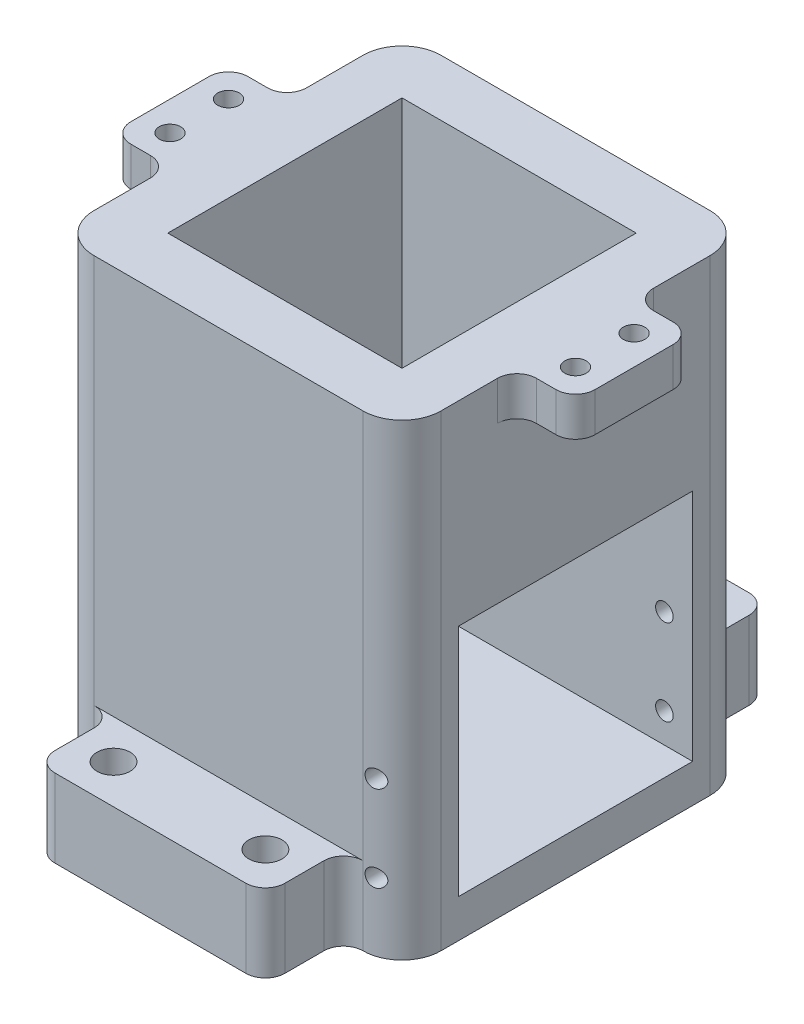
SolidWorks part; units mm, degrees
ref_plane "Front Plane" through (0, 0, 0) normal (0, 0, 1) x (1, 0, 0)
ref_plane "Top Plane" through (0, 0, 0) normal (0, 1, 0) x (1, 0, 0)
ref_plane "Right Plane" through (0, 0, 0) normal (1, 0, 0) x (0, 0, -1)
sketch "Sketch3" plane through (0, 0, 0) normal (0, 1, 0) x (1, 0, 0)
  line L1 (0, 0) -> (88.9, 0)
  line L2 (0, 0) -> (0, 88.9)
  line L3 (0, 88.9) -> (88.9, 88.9)
  line L4 (88.9, 0) -> (88.9, 88.9)
  dimension "D1" = 88.9
  dimension "D2" = 88.9
extrude "Boss-Extrude2" add sketch "Sketch3" along normal blind 50.8
ref_plane "Plane1" through (44.45, 0, 0) normal (-1, 0, 0) x (0, 0, 1)
sketch "Sketch5" plane through (0, 50.8, 0) normal (0, 1, 0) x (1, 0, 0)
  line L6 (0, 0) -> (88.9, 0)
  line L7 (0, 0) -> (0, 88.9)
  line L8 (0, 88.9) -> (88.9, 88.9)
  line L9 (88.9, 0) -> (88.9, 88.9)
sketch "Sketch7" plane through (0, 0, 0) normal (0, -1, 0) x (1, 0, 0)
  line L0 (44.45, -44.45) -> (65.45, -44.45)
  line L1 (44.45, 27.94) -> (44.45, -27.94) construction
  line L2 (65.45, -44.45) -> (65.45, -24.45)
  line L3 (65.45, -24.45) -> (23.45, -24.45)
  line L4 (23.45, -24.45) -> (23.45, -66.45)
  line L5 (23.45, -66.45) -> (65.45, -66.45)
  line L6 (65.45, -66.45) -> (65.45, -44.45)
  line L7 (44.45, -44.45) -> (44.45, -23.45)
  line L8 (44.45, -44.45) -> (44.45, -65.45)
  dimension "D1" = 21
  dimension "D3" = 42
  dimension "D4" = 42
  dimension "D5" = 21
  dimension "D6" = 21
sketch "Sketch10" plane through (0, 0, 0) normal (-1, 0, 0) x (0, 0, 1)
  line L1 (-73.9, 41) -> (-53.9, 41)
  line L2 (-73.9, 41) -> (-73.9, 61)
  line L3 (-73.9, 61) -> (-53.9, 61)
  line L4 (-53.9, 41) -> (-53.9, 61)
  line L5 (-88.9, 50.8) -> (-88.9, 0) construction
  line L6 (-35, 43.1973) -> (-15, 43.1973)
  line L7 (-35, 43.1973) -> (-35, 63.1973)
  line L8 (-35, 63.1973) -> (-15, 63.1973)
  line L9 (-15, 43.1973) -> (-15, 63.1973)
  line L11 (-88.9, 0) -> (0, 0) construction
  dimension "D1" = 20
  dimension "D2" = 20
  dimension "D3" = 20
  dimension "D4" = 20
  dimension "D5" = 18.9
  dimension "D6" = 15
  dimension "D7" = 41
sketch "Sketch11" plane through (88.9, 0, 0) normal (1, 0, 0) x (0, 0, -1)
  line L0 (0, 0) -> (88.9, 0) construction
  line L1 (15, 0) -> (35, 0)
  line L2 (15, 0) -> (15, 20)
  line L3 (15, 20) -> (35, 20)
  line L4 (35, 0) -> (35, 20)
  line L5 (0, 50.8) -> (0, 0) construction
  line L6 (53.9, 41) -> (73.9, 41)
  line L7 (53.9, 41) -> (53.9, 61)
  line L8 (53.9, 61) -> (73.9, 61)
  line L9 (73.9, 41) -> (73.9, 61)
  line L10 (88.9, 50.8) -> (88.9, 0) construction
  dimension "D1" = 20
  dimension "D2" = 20
  dimension "D3" = 15
  dimension "D4" = 15
sketch "Sketch13" plane through (0, 0, 0) normal (0, 0, 1) x (1, 0, 0)
  line L0 (44.45, 27.94) -> (44.45, -27.94) construction
  line L1 (0, 0) -> (88.9, 0) construction
  line L2 (88.9, 50.8) -> (88.9, 0) construction
  circle A0 centre (44.45, 20) radius 4.25
  dimension "D1" = 20
  dimension "D2" = 44.45
extrude "Cut-Extrude4" cut sketch "Sketch13" against normal blind 102
sketch "Sketch30" plane through (0, 50.8, 0) normal (0, 1, 0) x (1, 0, 0)
  line L1 (0, 0) -> (88.9, 0)
  line L2 (0, 0) -> (0, 88.9)
  line L3 (0, 88.9) -> (88.9, 88.9)
  line L4 (88.9, 0) -> (88.9, 88.9)
  line L5 (14.45, 74.45) -> (74.45, 74.45)
  line L6 (14.45, 74.45) -> (14.45, 14.45)
  line L7 (14.45, 14.45) -> (74.45, 14.45)
  line L8 (74.45, 74.45) -> (74.45, 14.45)
  dimension "D1" = 60
  dimension "D2" = 60
  dimension "D3" = 14.45
  dimension "D4" = 14.45
extrude "Boss-Extrude8" add sketch "Sketch30" along normal blind 110
sketch "Sketch31" plane through (0, 160.8, 0) normal (0, 1, 0) x (1, 0, 0)
  line L0 (0, 0) -> (0, 88.9) construction
  line L9 (0, 44.45) -> (-15, 44.45)
  line L10 (0, 44.45) -> (0, 59.45)
  line L11 (0, 59.45) -> (-15, 59.45)
  line L12 (-15, 44.45) -> (-15, 59.45)
  line L13 (88.9, 0) -> (88.9, 88.9) construction
  line L14 (0, 44.45) -> (-15, 44.45)
  line L15 (0, 44.45) -> (0, 29.45)
  line L16 (0, 29.45) -> (-15, 29.45)
  line L17 (-15, 44.45) -> (-15, 29.45)
  line L18 (88.9, 44.45) -> (103.9, 44.45)
  line L19 (88.9, 44.45) -> (88.9, 59.45)
  line L20 (88.9, 59.45) -> (103.9, 59.45)
  line L21 (103.9, 44.45) -> (103.9, 59.45)
  line L22 (0, 59.45) -> (0, 29.45)
  line L23 (88.9, 44.45) -> (103.9, 44.45)
  line L24 (88.9, 44.45) -> (88.9, 29.45)
  line L25 (88.9, 29.45) -> (103.9, 29.45)
  line L26 (103.9, 44.45) -> (103.9, 29.45)
  circle A6 centre (-7.5, 51.95) radius 2.75
  circle A7 centre (-7.5, 36.95) radius 2.75
  circle A8 centre (96.4, 51.95) radius 2.75
  circle A9 centre (96.4, 36.95) radius 2.75
  line M1 (0, 88.9) -> (0, 0)
  line M3 (88.9, 0) -> (88.9, 88.9)
  dimension "D1" = 15
  dimension "D5" = 15
  dimension "D2" = 15
  dimension "D3" = 15
  dimension "D4" = 15
  dimension "D6" = 15
  dimension "D7" = 15
  dimension "D8" = 15
extrude "Boss-Extrude10" add sketch "Sketch31" against normal blind 10 contours L12 L9 L11 A6 M1 | L9 L17 L16 A7 M1 | L18 L21 L20 A8 M3 | L26 L18 L25 A9 M3 region at (-0.2121, 160.8, -36.95) region at (-7.5, 160.8, -44.6621) region at (89.1121, 160.8, -51.95) region at (96.4, 160.8, -44.2379)
fillet "Fillet1" radius 10 4 edges at (0, 80.4, 0) (0, 80.4, -88.9) (88.9, 80.4, -88.9) (88.9, 80.4, 0)
sketch "Sketch33" plane through (88.9, 0, 0) normal (1, 0, 0) x (0, 0, -1)
  line L1 (14.45, 50.8) -> (74.45, 50.8)
  line L2 (14.45, 50.8) -> (14.45, 110.8)
  line L3 (14.45, 110.8) -> (74.45, 110.8)
  line L4 (74.45, 50.8) -> (74.45, 110.8)
  line L8 (0, 160.8) -> (0, 0) construction
  dimension "D1" = 60
  dimension "D2" = 60
  dimension "D3" = 14.45
extrude "Cut-Extrude5" cut sketch "Sketch33" against normal blind 20
sketch "Sketch36" plane through (88.9, 0, 0) normal (1, 0, 0) x (0, 0, -1)
  line L0 (0, 160.8) -> (0, 0) construction
  point P0 (0, 80.4)
sketch "Sketch37" plane through (0, 0, 0) normal (0, 0, 1) x (1, 0, 0)
  line L0 (88.9, 160.8) -> (88.9, 0) construction
  circle A0 centre (81.675, 80.4) radius 2.25
  circle A1 centre (81.675, 58.4) radius 2.25
  dimension "D1" = 7.225
  dimension "D2" = 7.225
  dimension "D3" = 22
extrude "Cut-Extrude6" cut sketch "Sketch37" against normal blind 113
sketch "Sketch38" plane through (0, 0, 0) normal (0, -1, 0) x (1, 0, 0)
  line L1 (88.9, -88.9) -> (0, -88.9)
  line L2 (88.9, -88.9) -> (88.9, 0)
  line L3 (88.9, 0) -> (0, 0)
  line L4 (0, -88.9) -> (0, 0)
  line L5 (88.9, -88.9) -> (0, 0) construction
  line L6 (88.9, 0) -> (0, -88.9) construction
  point P0 (44.45, -44.45)
extrude "Cut-Extrude7" cut sketch "Sketch38" against normal blind 41
sketch "Sketch39" plane through (0, 0, 0) normal (0, 0, 1) x (1, 0, 0)
  line L0 (78.9, 41) -> (10, 41) construction
  line L1 (44.45, 41) -> (73.9, 41)
  line L2 (44.45, 41) -> (44.45, 61)
  line L3 (44.45, 61) -> (73.9, 61)
  line L4 (73.9, 41) -> (73.9, 61)
  line L6 (44.45, 41) -> (15, 41)
  line L7 (44.45, 41) -> (44.45, 61)
  line L8 (44.45, 61) -> (15, 61)
  line L9 (15, 41) -> (15, 61)
  line M7 (10, 41) -> (78.9, 41)
  dimension "D1" = 29.45
  dimension "D2" = 29.45
  dimension "D3" = 20
sketch "Sketch40" plane through (0, 0, -88.9) normal (0, 0, -1) x (-1, 0, 0)
  line L1 (-44.45, 41) -> (-15, 41)
  line L2 (-44.45, 41) -> (-44.45, 61)
  line L3 (-44.45, 61) -> (-15, 61)
  line L4 (-15, 41) -> (-15, 61)
  line L5 (-44.45, 41) -> (-73.9, 41)
  line L6 (-44.45, 41) -> (-44.45, 61)
  line L7 (-44.45, 61) -> (-73.9, 61)
  line L8 (-73.9, 41) -> (-73.9, 61)
  line M7 (-78.9, 41) -> (-10, 41)
  dimension "D1" = 29.45
  dimension "D2" = 29.45
  dimension "D3" = 20
extrude "Boss-Extrude11" add sketch "Sketch39" along normal blind 20 contours L9 L2 L8 M7 | L4 L3 L2 M7 region at (59.175, 51, 0) region at (29.725, 51, 0)
extrude "Boss-Extrude12" add sketch "Sketch40" along normal blind 20 contours L8 L2 L7 M7 | L4 L3 L2 M7 region at (29.725, 51, -88.9) region at (59.175, 51, -88.9)
sketch "Sketch41" plane through (0, 41, 0) normal (0, -1, 0) x (1, 0, 0)
  line L0 (73.9, 20) -> (73.9, 0) construction
  line L1 (15, 20) -> (73.9, 20) construction
  line L2 (15, 20) -> (15, 0) construction
  line L3 (73.9, -108.9) -> (15, -108.9) construction
  line L4 (73.9, -108.9) -> (73.9, -88.9) construction
  line L5 (15, -108.9) -> (15, -88.9) construction
  circle A0 centre (63.9, 10) radius 4.25
  circle A1 centre (25, 10) radius 4.25
  circle A2 centre (63.9, -98.9) radius 4.25
  circle A3 centre (25, -98.9) radius 4.25
  dimension "D1" = 10
  dimension "D2" = 10
  dimension "D3" = 10
  dimension "D4" = 10
  dimension "D5" = 10
  dimension "D6" = 10
  dimension "D7" = 10
  dimension "D8" = 10
extrude "Cut-Extrude8" cut sketch "Sketch41" against normal blind 20
fillet "Fillet2" radius 5 8 edges at (15, 51, -108.9) (15, 51, -88.9) (73.9, 51, -108.9) (73.9, 51, -88.9) (73.9, 51, 0) (15, 51, 0) (15, 51, 20) (73.9, 51, 20)
fillet "Fillet3" radius 5 8 edges at (103.9, 155.8, -59.45) (88.9, 155.8, -59.45) (103.9, 155.8, -29.45) (88.9, 155.8, -29.45) (-15, 155.8, -29.45) (0, 155.8, -29.45) (0, 155.8, -59.45) (-15, 155.8, -59.45)
